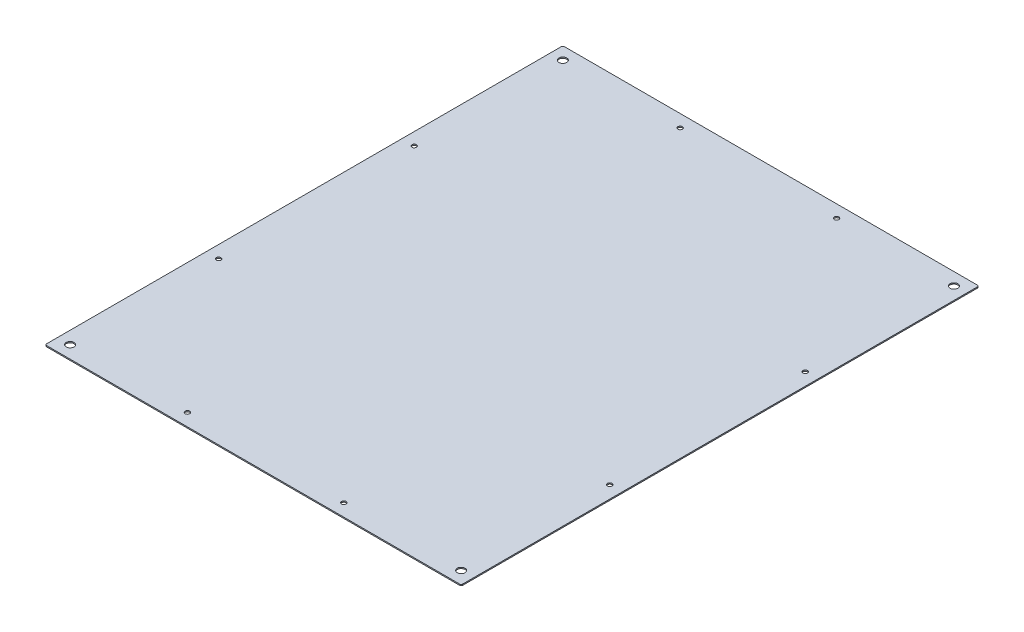
SolidWorks part; units mm, degrees
note: The reader was unsure of these and kept them because the rebuilt part matched: thickness of "Base-Flange1", "Sheet-Metal1", "Sheet-Metal3", "Sheet-Metal6".
material "3.3547 (EN-AW 5083)"
ref_plane "Front Plane" through (0, 0, 0) normal (0, 0, 1) x (1, 0, 0)
ref_plane "Top Plane" through (0, 0, 0) normal (0, 1, 0) x (1, 0, 0)
ref_plane "Right Plane" through (0, 0, 0) normal (1, 0, 0) x (0, 0, -1)
sketch "Sketch1" plane through (0, 0, 0) normal (0, 1, 0) x (0, 0, -1)
  line L1 (331, -266) -> (-331, -266)
  line L2 (331, -266) -> (331, 266)
  line L3 (331, 266) -> (-331, 266)
  line L4 (-331, -266) -> (-331, 266)
  line L5 (331, -266) -> (-331, 266) construction
  line L6 (331, 266) -> (-331, -266) construction
  point P0 (0, 0)
  dimension "D1" = 532
  dimension "D2" = 662
  dimension "D3" = 0
base flange "Base-Flange1" sketch "Sketch1" thickness 1.5 reverse thickness direction no parameters "D1"=0.7366
fillet "Fillet1" radius 2 4 edges at (266, -0.75, -331) (-266, -0.75, -331) (266, -0.75, 331) (-266, -0.75, 331)
hole_wizard "M8 Clearance Hole1" positions "Sketch5" profile "Sketch6" hole size "M8" standard "DIN" end condition up to next
sketch "Sketch5" plane through (0, 0, 0) normal (0, 1, 0) x (1, 0, 0)
  line L0 (-250, -315) -> (250, -315) construction
  line L4 (-264, -331) -> (264, -331) construction
  line L6 (-266, 329) -> (-266, -329) construction
  line L7 (266, -329) -> (266, 329) construction
  line L8 (0, 0) -> (266, 0) construction
  point P0 (-250, -315)
  point P25 (250, -315)
  point P27 (250, 315)
  point P28 (-250, 315)
  dimension "D1" = 16
  dimension "D2" = 16
  dimension "D3" = 16
sketch "Sketch6" plane through (-250, 0, 315) normal (1, 0, 0) x (0, 0, 1)
  line L0 (0, 0) -> (0, 1.5)
  line L1 (0, 1.5) -> (5, 1.5)
  line L2 (5, 1.5) -> (5, 0)
  line L5 (5, 0) -> (0, 0)
  line L11 (0, -6.35) -> (0, 107.95) construction
  dimension "Thru Hole Dia." = 10
  dimension "Thru Hole Depth" = 1.5
hole_wizard "M5 Clearance Hole1" positions "Sketch7" profile "Sketch8" hole size "M5" standard "DIN" end condition up to next
sketch "Sketch7" plane through (0, 0, 0) normal (0, 1, 0) x (1, 0, 0)
  line L0 (0, 0) -> (0, 331) construction
  line L1 (264, 331) -> (-264, 331) construction
  line L2 (0, 0) -> (-266, 0) construction
  line L3 (-266, 329) -> (-266, -329) construction
  line L5 (-250, 315) -> (-250, 125) construction
  line L7 (-250, 315) -> (-100, 315) construction
  point P8 (-100, 315)
  point P10 (-250, 125)
  point P12 (-250, -125)
  point P32 (-100, -315)
  point P33 (100, -315)
  point P34 (250, -125)
  point P35 (250, 125)
  point P36 (100, 315)
  dimension "D1" = 250
  dimension "D2" = 200
sketch "Sketch8" plane through (100, 0, -315) normal (1, 0, 0) x (0, 0, 1)
  line L0 (0, 0) -> (0, 1.5)
  line L1 (0, 1.5) -> (2.9, 1.5)
  line L2 (2.9, 1.5) -> (2.9, 0)
  line L5 (2.9, 0) -> (0, 0)
  line L11 (0, -6.35) -> (0, 107.95) construction
  dimension "Thru Hole Dia." = 5.8
  dimension "Thru Hole Depth" = 1.5
sketch "Bend-Lines1" [suppressed] plane through (0, 0, 0) normal (0, 1, 0) x (1, 0, 0)
sketch "Bounding-Box1" [suppressed] plane through (0, 0, 0) normal (0, 1, 0) x (1, 0, 0)
sheet metal parameters "Sheet-Metal1" thickness 1.5 parameters "D1"=0.7366, "D7"=2
flat pattern "Flat-Pattern1" [suppressed]
sketch "Bend-Lines2" plane through (0, 0, 0) normal (0, 1, 0) x (1, 0, 0)
sketch3d "Bounding-Box2" [suppressed]
  line L0 (-235, 280, 0) -> (-235, -340, 0) construction
  line L1 (235, 280, 0) -> (235, -340, 0) construction
  line L2 (-235, 280, 0) -> (235, 280, 0) construction
  line L3 (-235, -340, 0) -> (235, -340, 0) construction
sheet metal parameters "Sheet-Metal3" thickness 1.5 parameters "D1"=0.7366, "D7"=2
flat pattern "Flat-Pattern1"
sketch "Bend-Lines2" plane through (0, 0, 0) normal (0, 1, 0) x (1, 0, 0)
sketch3d "Bounding-Box2" [suppressed]
  line L0 (262.5004, 327.4997, 0) -> (262.5, -327.5, 0) construction
  line L1 (-262.4996, 327.5, 0) -> (-262.5, -327.4997, 0) construction
  line L2 (262.5004, 327.4997, 0) -> (-262.4996, 327.5, 0) construction
  line L3 (262.5, -327.5, 0) -> (-262.5, -327.4997, 0) construction
sheet metal parameters "Sheet-Metal6" thickness 1.5 parameters "D1"=0.7366, "D7"=2
flat pattern "Flat-Pattern1"
sketch "Bend-Lines2" plane through (0, 0, 0) normal (0, 1, 0) x (1, 0, 0)
sketch3d "Bounding-Box2" [suppressed]
  line L0 (266.0004, 330.9997, 0) -> (266, -331, 0) construction
  line L1 (-265.9996, 331, 0) -> (-266, -330.9997, 0) construction
  line L2 (266.0004, 330.9997, 0) -> (-265.9996, 331, 0) construction
  line L3 (266, -331, 0) -> (-266, -330.9997, 0) construction
